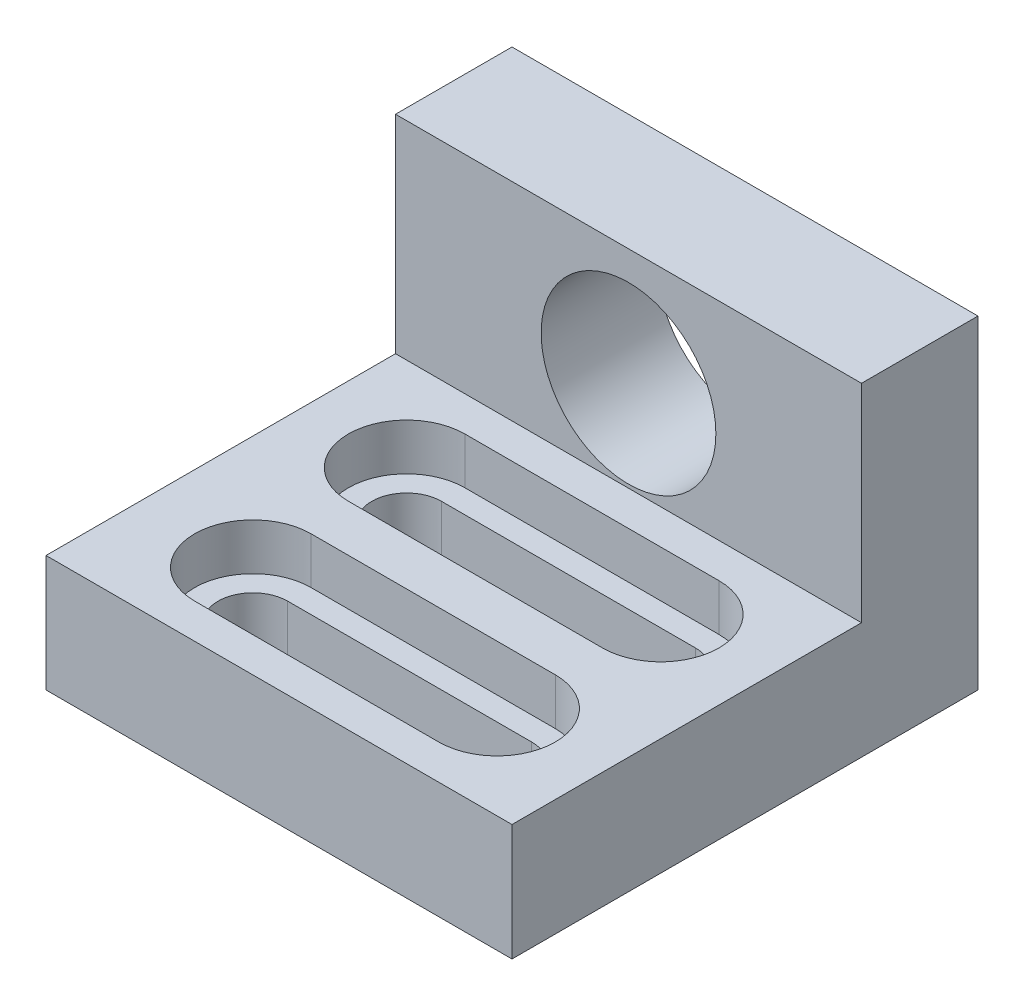
SolidWorks part; units mm, degrees
ref_plane "Front Plane" through (0, 0, 0) normal (0, 0, 1) x (1, 0, 0)
ref_plane "Top Plane" through (0, 0, 0) normal (0, 1, 0) x (1, 0, 0)
ref_plane "Right Plane" through (0, 0, 0) normal (1, 0, 0) x (0, 0, -1)
sketch "Sketch1" plane through (0, 0, 0) normal (0, 0, 1) x (1, 0, 0)
  line L0 (-12.7, 0) -> (-12.7, -11.303)
  line L1 (-12.7, -11.303) -> (12.7, -11.303)
  line L2 (12.7, -11.303) -> (12.7, 0)
  line L3 (-12.7, 0) -> (-12.7, 6.35)
  line L4 (-12.7, 6.35) -> (12.7, 6.35)
  line L5 (12.7, 6.35) -> (12.7, 0)
  circle A1 centre (0, 0) radius 4.7625
  dimension "D1" = 6.35
  dimension "D2" = 9.525
  dimension "D3" = 11.303
  dimension "D4" = 25.4
  dimension "D5" = 12.7
extrude "Boss-Extrude1" add sketch "Sketch1" along normal blind 6.35
sketch "Sketch2" plane through (0, 0, 6.35) normal (0, 0, 1) x (1, 0, 0)
  line L0 (12.7, -11.303) -> (12.7, 6.35) construction
  line L1 (-12.7, -11.303) -> (12.7, -11.303)
  line L2 (-12.7, -11.303) -> (-12.7, -4.953)
  line L3 (-12.7, -4.953) -> (12.7, -4.953)
  line L4 (12.7, -11.303) -> (12.7, -4.953)
  dimension "D1" = 6.35
extrude "Boss-Extrude2" add sketch "Sketch2" along normal blind 19.05
sketch "Sketch8" plane through (0, -4.953, 0) normal (0, 1, 0) x (1, 0, 0)
  line L0 (12.7, -6.35) -> (-12.7, -6.35) construction
  line L9 (-7.021, -9.525) -> (6.8319, -9.525)
  line L11 (-7.021, -13.3223) -> (6.8319, -13.3223)
  line L13 (-6.4982, -18.4284) -> (6.793, -18.4284)
  line L23 (-6.4472, -22.225) -> (6.8651, -22.225)
  line L25 (12.7, -25.4) -> (-12.7, -25.4) construction
  line L27 (-6.4982, -17.152) -> (6.811, -17.152)
  line L29 (-6.4982, -23.502) -> (6.811, -23.502)
  line L31 (-7.021, -8.2486) -> (6.8319, -8.2486)
  line L33 (-7.021, -14.5986) -> (6.8319, -14.5986)
  arc A6 (-7.021, -9.525) -> (-7.021, -13.3223) centre (-7.021, -11.4237) ccw
  arc A7 (6.8319, -13.3223) -> (6.8319, -9.525) centre (6.8319, -11.4236) ccw
  arc A8 (6.8651, -22.225) -> (6.793, -18.4284) centre (6.811, -20.327) ccw
  arc A9 (-6.4982, -18.4284) -> (-6.4472, -22.225) centre (-6.4982, -20.327) ccw
  arc A10 (-7.021, -8.2486) -> (-7.021, -14.5986) centre (-7.021, -11.4237) ccw
  arc A12 (6.811, -23.502) -> (6.811, -17.152) centre (6.811, -20.327) ccw
  arc A13 (-6.4982, -17.152) -> (-6.4982, -23.502) centre (-6.4982, -20.327) ccw
  arc A15 (6.8319, -14.5986) -> (6.8319, -8.2486) centre (6.8319, -11.4236) ccw
  dimension "D1" = 3.7973
  dimension "D2" = 3.7973
  dimension "D3" = 3.175
  dimension "D4" = 3.175
extrude "Cut-Extrude1" cut sketch "Sketch8" against normal blind 2.54 contours L11 A7 L9 A6 | L13 A9 L23 A8 | L27 A13 L29 A12 A9 L13 A8 L23 | L33 A15 L31 A10 A7 L11 A6 L9 region at (-0.0946, -4.953, 11.4236) region at (0.1565, -4.953, 20.3268) region at (0.1564, -4.953, 17.3586) region at (-0.0946, -4.953, 8.4604)
extrude "Cut-Extrude2" cut sketch "Sketch8<12>" against normal through all contours L13 A9 L23 A8 | L11 A7 L9 A6 region at (-0.0946, -4.953, 11.4236) region at (0.1565, -4.953, 20.3268)
sketch "Sketch8<12>" plane through (0, -4.953, 0) normal (0, 1, 0) x (1, 0, 0) same geometry as "Sketch8"
